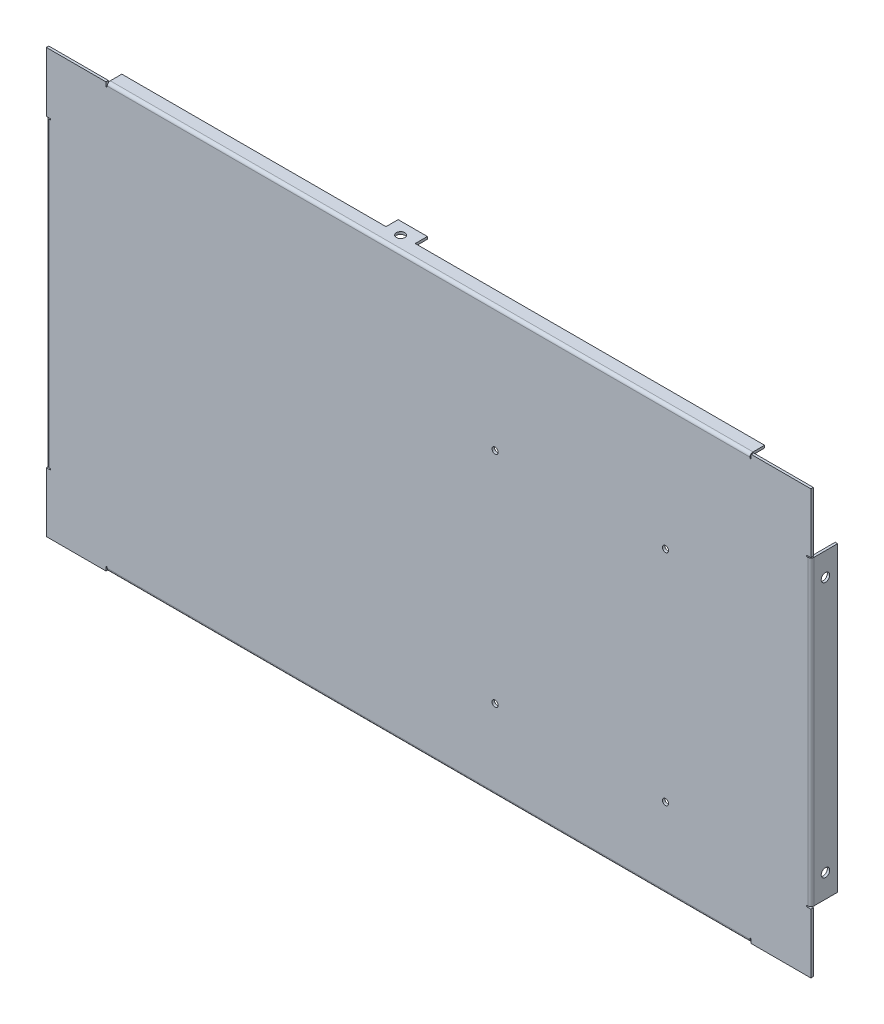
SolidWorks part; units mm, degrees
note: The reader was unsure of these and kept them because the rebuilt part matched: flange length of "边线-法兰1", "边线-法兰2", "边线-法兰3", "边线-法兰4".
ref_plane "前视基准面" through (0, 0, 0) normal (0, 0, 1) x (1, 0, 0)
ref_plane "上视基准面" through (0, 0, 0) normal (0, 1, 0) x (1, 0, 0)
ref_plane "右视基准面" through (0, 0, 0) normal (1, 0, 0) x (0, 0, -1)
sketch "草图1" plane through (0, 0, 0) normal (0, 0, 1) x (1, 0, 0)
  line L1 (-314, 174) -> (314, 174)
  line L2 (-314, 174) -> (-314, -174)
  line L3 (-314, -174) -> (314, -174)
  line L4 (314, 174) -> (314, -174)
  line L5 (-314, 174) -> (314, -174) construction
  line L6 (-314, -174) -> (314, 174) construction
  point P0 (0, 0)
  dimension "D1" = 628
  dimension "D2" = 348
sheet metal parameters "钣金1" thickness 2 parameters "D1"=0.5
base flange "基体-法兰1" sketch "草图1" thickness 2 reverse thickness direction no parameters "D1"=0.5
edge flange "边线-法兰1" sketch "草图5" flange angle 90 flange length 22 flange position material inside bend radius 0.5 thickness 2 relief rectangular parameters "D6"=10
sketch "草图5" plane through (314, 0, -2) normal (1, 0, 0) x (0, -1, 0)
  line L0 (174, 0) -> (-174, 0) construction
  line L1 (124, 0) -> (-124, 0)
  line L2 (-124, 0) -> (-124, 20)
  line L3 (-124, 20) -> (124, 20)
  line L4 (124, 20) -> (124, 0)
  line L5 (-174, 0) -> (-174, -2) construction
  line L6 (174, 0) -> (174, -2) construction
  line L7 (174, -2) -> (-174, -2) construction
  dimension "D1" = 50
  dimension "D2" = 50
  dimension "D3" = 22
bend "边线折弯1" bend radius 0.5 bend angle 90 parameters "D5"=1
edge flange "边线-法兰2" sketch "草图8" flange angle 90 flange length 22 flange position material inside bend radius 0.5 thickness 2 relief rectangular parameters "D6"=10
sketch "草图8" plane through (0, 174, -2) normal (0, 1, 0) x (1, 0, 0)
  line L0 (314, 0) -> (-314, 0) construction
  line L1 (264, 0) -> (-264, 0)
  line L2 (-264, 0) -> (-264, 10)
  line L3 (-264, 10) -> (-47, 10)
  line L4 (264, 10) -> (264, 0)
  line L5 (-314, 0) -> (-314, -2) construction
  line L6 (314, 0) -> (314, -2) construction
  line L7 (314, -2) -> (-314, -2) construction
  line L8 (-23, 10) -> (264, 10)
  line L10 (-23, 10) -> (-23, 20)
  line L11 (-23, 20) -> (-47, 20)
  line L12 (-47, 10) -> (-47, 20)
  dimension "D1" = 50
  dimension "D2" = 50
  dimension "D3" = 12
  dimension "D4" = 337
  dimension "D5" = 24
  dimension "D6" = 22
bend "边线折弯2" bend radius 0.5 bend angle 90 parameters "D5"=2
edge flange "边线-法兰3" sketch "草图11" flange angle 90 flange length 22 flange position material inside bend radius 0.5 thickness 2 relief rectangular parameters "D6"=10
sketch "草图11" plane through (-314, 0, -2) normal (-1, 0, 0) x (0, 1, 0)
  line L0 (174, 0) -> (-174, 0) construction
  line L1 (124, 0) -> (-124, 0)
  line L2 (-124, 0) -> (-124, 20)
  line L3 (-124, 20) -> (124, 20)
  line L4 (124, 20) -> (124, 0)
  line L5 (-174, 0) -> (-174, -2) construction
  line L6 (174, 0) -> (174, -2) construction
  line L7 (174, -2) -> (-174, -2) construction
  dimension "D1" = 50
  dimension "D2" = 50
  dimension "D3" = 22
bend "边线折弯3" bend radius 0.5 bend angle 90 parameters "D5"=3
edge flange "边线-法兰4" sketch "草图14" flange angle 90 flange length 22 flange position material inside bend radius 0.5 thickness 2 relief rectangular parameters "D6"=10
sketch "草图14" plane through (0, -174, -2) normal (0, -1, 0) x (-1, 0, 0)
  line L0 (314, 0) -> (-314, 0) construction
  line L1 (264, 0) -> (-264, 0)
  line L2 (-264, 0) -> (-264, 20)
  line L3 (-264, 20) -> (264, 20)
  line L4 (264, 20) -> (264, 0)
  line L5 (314, 0) -> (314, -2) construction
  line L6 (-314, 0) -> (-314, -2) construction
  line L7 (314, -2) -> (-314, -2) construction
  dimension "D1" = 50
  dimension "D2" = 50
  dimension "D3" = 22
bend "边线折弯4" bend radius 0.5 bend angle 90 parameters "D5"=4
sketch "草图15" plane through (314, 0, 0) normal (1, 0, 0) x (0, 0, -1)
  line L0 (22, 0) -> (0, 0) construction
  line L1 (22, -124) -> (22, 124) construction
  circle A0 centre (12, -105) radius 3.5
  circle A1 centre (12, 105) radius 3.5
  dimension "D2" = 7
  dimension "D1" = 210
  dimension "D3" = 10
extrude "切除-拉伸1" cut sketch "草图15" against normal through all normal cut yes
sketch "草图16" plane through (0, 172, 0) normal (0, -1, 0) x (1, 0, 0)
  line L0 (-23, -22) -> (-47, -22) construction
  line L1 (314, -2) -> (314, 0) construction
  circle A0 centre (-35, -12) radius 3.5
  dimension "D2" = 7
  dimension "D1" = 10
  dimension "D3" = 349
extrude "切除-拉伸2" cut sketch "草图16" against normal up to next normal cut yes
sketch "草图17" plane through (0, 0, -2) normal (0, 0, -1) x (-1, 0, 0)
  line L0 (-265, -174) -> (-314, -174) construction
  line L1 (-194.6, -108.5) -> (-54.6, -108.5) construction
  line L2 (-194.6, -108.5) -> (-194.6, 71.5) construction
  line L3 (-194.6, 71.5) -> (-54.6, 71.5) construction
  line L4 (-54.6, -108.5) -> (-54.6, 71.5) construction
  line L5 (-314, -174) -> (-314, -125) construction
  dimension "D1" = 140
  dimension "D2" = 180
  dimension "D3" = 65.5
  dimension "D4" = 119.4
hole_wizard "M6 螺纹孔1" positions "草图19" profile "草图18" tap size "M6" standard "GB"
sketch "草图19" plane through (0, 0, -2) normal (0, 0, -1) x (-1, 0, 0)
  point P1 (-194.6, 71.5)
  point P4 (-54.6, 71.5)
  point P7 (-54.6, -108.5)
  point P10 (-194.6, -108.5)
sketch "草图18" plane through (194.6, 71.5, -2) normal (1, 0, 0) x (0, 1, 0)
  line L0 (0, 0) -> (0, 16.5022)
  line L1 (0, 16.5022) -> (2.5, 15)
  line L2 (2.5, 15) -> (2.5, 0)
  line L5 (2.5, 0) -> (0, 0)
  line L10 (0, 16.5022) -> (-2.5, 15) construction
  line L11 (0, -6.35) -> (0, 107.95) construction
  dimension "螺纹孔钻头直径" = 5
  dimension "螺纹孔钻头深度" = 15
  dimension "导头角度" = 118
cosmetic thread "孔螺蚊线1" parameters "D1"=2, "D2"=6
cosmetic thread "孔螺蚊线2" parameters "D1"=2, "D2"=6
cosmetic thread "孔螺蚊线3" parameters "D1"=2, "D2"=6
cosmetic thread "孔螺蚊线4" parameters "D1"=2, "D2"=6
sketch "草图20" plane through (0, -174, 0) normal (0, -1, 0) x (1, 0, 0)
  line L0 (0, -22) -> (0, -2.5) construction
  line L1 (-264, -22) -> (264, -22) construction
  line L2 (-264, -2.5) -> (264, -2.5) construction
  circle A0 centre (0, -12) radius 3.5
  circle A1 centre (-250, -12) radius 3.5
  circle A2 centre (250, -12) radius 3.5
  dimension "D3" = 7
  dimension "D1" = 250
  dimension "D2" = 250
  dimension "D4" = 10
extrude "切除-拉伸3" cut sketch "草图20" against normal up to next normal cut yes
flat pattern "平板型式1" [suppressed]
sketch "折弯-线1" plane through (0, 0, 0) normal (0, 1, 0) x (-1, 0, 0)
bend of the flat pattern "展开-<边线折弯1>1"
bend of the flat pattern "展开-<边线折弯2>1"
bend of the flat pattern "展开-<边线折弯3>1"
bend of the flat pattern "展开-<边线折弯4>1"
